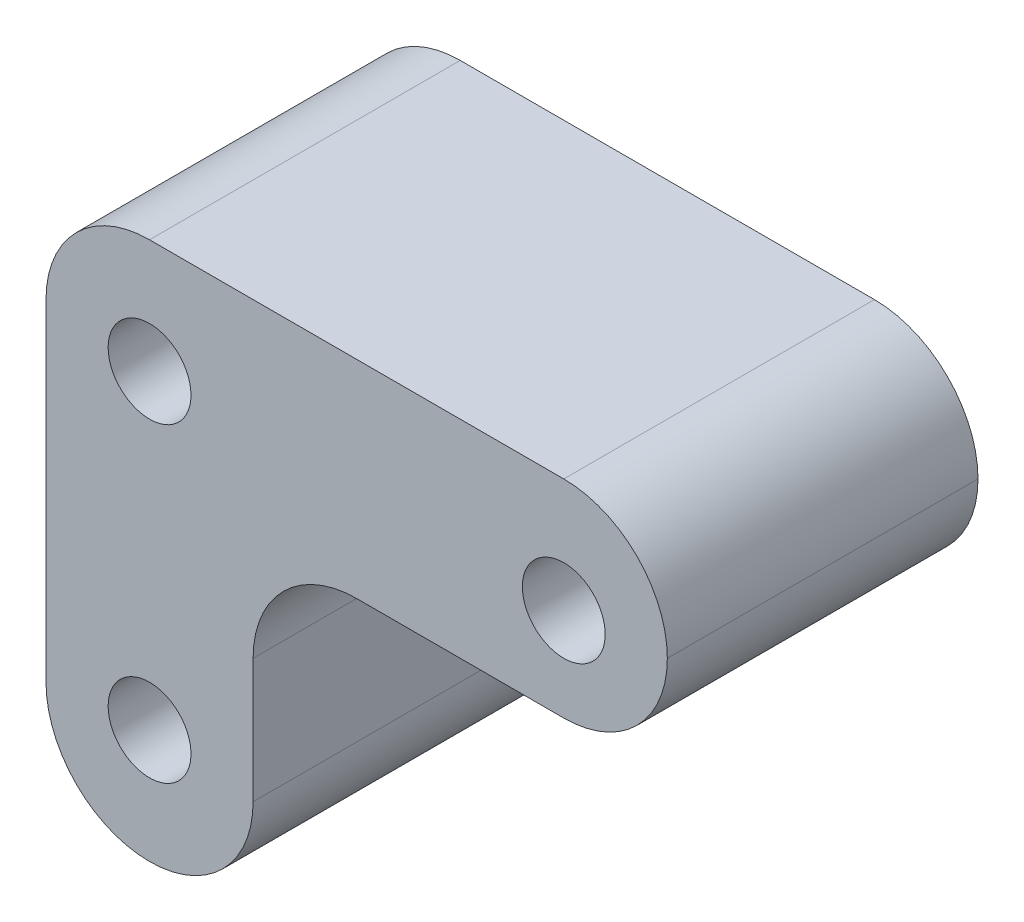
SolidWorks part; units mm, degrees
ref_plane "Front" through (0, 0, 0) normal (0, 0, 1) x (1, 0, 0)
ref_plane "Top" through (0, 0, 0) normal (0, 1, 0) x (1, 0, 0)
ref_plane "Right" through (0, 0, 0) normal (1, 0, 0) x (0, 0, -1)
sketch "Esquisse1" plane through (0, 0, 0) normal (0, 0, 1) x (1, 0, 0)
  line L1 (0, 0) -> (30, 0)
  line L2 (0, 0) -> (0, 26)
  line L3 (0, 26) -> (30, 26)
  line L4 (30, 0) -> (30, 26)
  dimension "D1" = 30
  dimension "D2" = 26
extrude "Boss.-Extru.1" add sketch "Esquisse1" along normal blind 15
sketch "Esquisse2" plane through (0, 0, 15) normal (0, 0, 1) x (1, 0, 0)
  line L0 (15, 0) -> (15, 26) construction
  line L1 (0, 0) -> (30, 0) construction
  line L2 (30, 26) -> (0, 26) construction
  line L3 (15, 13) -> (0, 13) construction
  line L4 (0, 26) -> (0, 0) construction
  circle A0 centre (5, 20.5) radius 2
  circle A1 centre (25, 20.5) radius 2
  circle A2 centre (25, 5.5) radius 2
  circle A3 centre (5, 5.5) radius 2
  dimension "D1" = 15
  dimension "D2" = 20
  dimension "D3" = 4
extrude "Enlèv. mat.-Extru.1" cut sketch "Esquisse2" against normal through all both and the other way through all
sketch "Esquisse3" plane through (0, 0, 15) normal (0, 0, 1) x (1, 0, 0)
  line L0 (30, 26) -> (0, 26) construction
  line L1 (30, 0) -> (10, 0)
  line L2 (30, 0) -> (30, 16)
  line L3 (30, 16) -> (10, 16)
  line L4 (10, 0) -> (10, 16)
  line L5 (0, 26) -> (0, 0) construction
  dimension "D1" = 10
  dimension "D2" = 10
extrude "Enlèv. mat.-Extru.2" cut sketch "Esquisse3" against normal through all both and the other way through all
fillet "Congé1" radius 5 6 edges at (10, 16, 7.5) (0, 26, 7.5) (0, 0, 7.5) (10, 0, 7.5) (30, 26, 7.5) (30, 16, 7.5)
